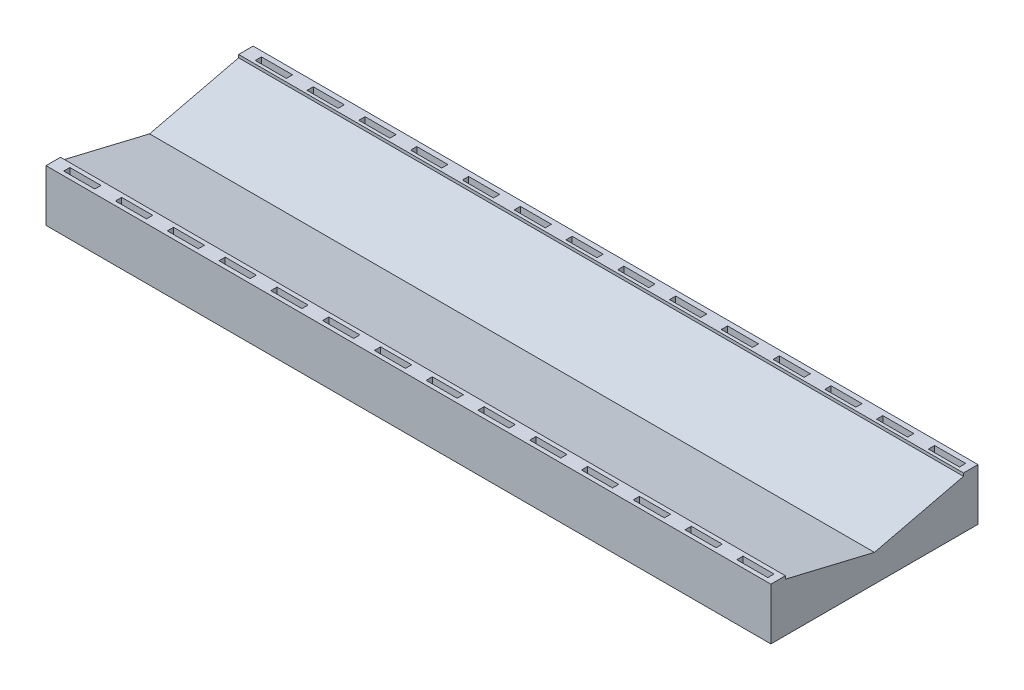
SolidWorks part; units mm, degrees
note: The reader was unsure of these and kept them because the rebuilt part matched: shared geometry of "Sketch3<3>".
ref_plane "Front Plane" through (0, 0, 0) normal (0, 0, 1) x (1, 0, 0)
ref_plane "Top Plane" through (0, 0, 0) normal (0, 1, 0) x (1, 0, 0)
ref_plane "Right Plane" through (0, 0, 0) normal (1, 0, 0) x (0, 0, -1)
sketch "Sketch1" plane through (0, 0, 0) normal (0, 1, 0) x (1, 0, 0)
  line L1 (0, 0) -> (35, 0)
  line L2 (0, 0) -> (0, 10)
  line L3 (0, 10) -> (35, 10)
  line L4 (35, 0) -> (35, 10)
  dimension "D1" = 35
  dimension "D2" = 10
extrude "Boss-Extrude1" add sketch "Sketch1" along normal blind 2.5
sketch "Sketch2" plane through (0, 2.5, 0) normal (0, 1, 0) x (1, 0, 0)
  line L0 (0, 10) -> (0, 0) construction
  line L1 (0.654, 0.2) -> (2.154, 0.2)
  line L2 (0.654, 0.2) -> (0.654, 0.5)
  line L3 (0.654, 0.5) -> (2.154, 0.5)
  line L4 (2.154, 0.2) -> (2.154, 0.5)
  line L5 (0, 0) -> (35, 0) construction
  dimension "D1" = 0.3
  dimension "D2" = 0.654
  dimension "D3" = 1.5
  dimension "D4" = 0.2
extrude "Cut-Extrude1" cut sketch "Sketch2" against normal blind 2
pattern_linear "LPattern1" count 14 spacing 2.5 along (1, 0, 0) count 2 spacing 9.25 along (0, 0, -1) of "Cut-Extrude1"
sketch "Sketch3" plane through (0, 0, 0) normal (-1, 0, 0) x (0, 0, 1)
  line L0 (-9.299, 2.5) -> (-9.299, 2.358)
  line L1 (-10, 2.5) -> (0, 2.5) construction
  line L2 (-9.299, 2.358) -> (-5, 1.3292)
  line L3 (-5, 1.3292) -> (-5, 1.1199)
  line L4 (-0.701, 2.358) -> (-5, 1.3292)
  line L5 (-0.701, 2.5) -> (-0.701, 2.358)
  line L6 (-5, 2.5) -> (-5, 0) construction
  line L7 (-10, 0) -> (0, 0) construction
  line M6 (0, 2.5) -> (-10, 2.5)
extrude "Cut-Extrude2" cut sketch "Sketch3" against normal through all contours L5 L0 L2 L4 M6
extrude "Cut-Extrude3" cut sketch "Sketch3<3>" against normal through all contours L6 L0 L2 M6
sketch "Sketch3<3>" plane through (0, 0, 0) normal (-1, 0, 0) x (0, 0, 1) same geometry as "Sketch3"
